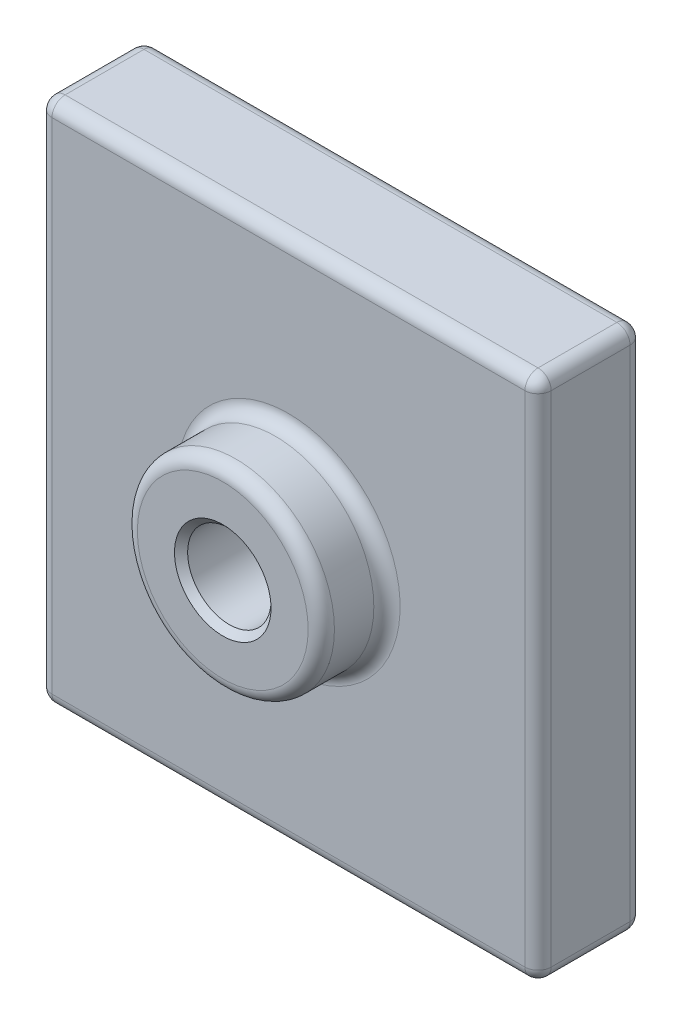
SolidWorks part; units mm, degrees
ref_plane "Front Plane" through (0, 0, 0) normal (0, 0, 1) x (1, 0, 0)
ref_plane "Top Plane" through (0, 0, 0) normal (0, 1, 0) x (1, 0, 0)
ref_plane "Right Plane" through (0, 0, 0) normal (1, 0, 0) x (0, 0, -1)
sketch "Sketch1" plane through (0, 0, 0) normal (0, 0, 1) x (1, 0, 0)
  line L1 (0, 0) -> (38, 0)
  line L2 (0, 0) -> (0, 40)
  line L3 (0, 40) -> (38, 40)
  line L4 (38, 0) -> (38, 40)
  dimension "D1" = 38
  dimension "D2" = 40
extrude "Boss-Extrude1" add sketch "Sketch1" along normal blind 8
sketch "Sketch2" plane through (0, 0, 8) normal (0, 0, 1) x (1, 0, 0)
  line L4 (0, 40) -> (0, 0)
  line L5 (0, 0) -> (38, 0)
  line L6 (38, 0) -> (38, 40)
  line L7 (38, 40) -> (0, 40)
  line L8 (0, 40) -> (0, 0) construction
  line L9 (0, 0) -> (38, 0) construction
  line L10 (38, 0) -> (38, 40) construction
  line L11 (38, 40) -> (0, 40) construction
  circle A0 centre (19, 20) radius 7.5
  circle A1 centre (19, 20) radius 3.175
  point P2 (19, 20)
  point P4 (0, 20)
  point P6 (19, 0)
  dimension "D2" = 15
  dimension "D3" = 6.35
  dimension "D1" = 0
extrude "Boss-Extrude2" add sketch "Sketch2" along normal blind 5
fillet "Fillet1" radius 1 14 edges at (26.5, 20, 13) (19, 0, 0) (19, 40, 0) (38, 0, 4) (38, 40, 4) (38, 20, 0) (0, 40, 4) (0, 0, 4) (0, 20, 0) (26.5, 20, 8) (19, 40, 8) (38, 20, 8) (19, 0, 8) (0, 20, 8)
sketch "Sketch3" plane through (0, 0, 0) normal (0, 0, -1) x (-1, 0, 0)
  line L4 (-1, 39) -> (-37, 39)
  line L5 (-37, 39) -> (-37, 1)
  line L6 (-37, 1) -> (-1, 1)
  line L7 (-1, 1) -> (-1, 39)
  line L8 (-1, 39) -> (-37, 39) construction
  line L9 (-37, 39) -> (-37, 1) construction
  line L10 (-37, 1) -> (-1, 1) construction
  line L11 (-1, 1) -> (-1, 39) construction
  line L15 (-15.7921, 25.5563) -> (-22.2079, 25.5563)
  line L16 (-22.2079, 25.5563) -> (-25.4158, 20)
  line L17 (-25.4158, 20) -> (-22.2079, 14.4438)
  line L18 (-22.2079, 14.4438) -> (-15.7921, 14.4438)
  line L19 (-15.7921, 14.4438) -> (-12.5842, 20)
  line L20 (-12.5842, 20) -> (-15.7921, 25.5563)
  circle A0 centre (-19, 20) radius 5.5562 construction
  point P2 (-19, 39)
  point P4 (-37, 20)
  point P6 (-19, 20)
  dimension "D2" = 11.1125
  dimension "D1" = 0
extrude "Cut-Extrude1" cut sketch "Sketch3" against normal blind 5.5562
sketch "Sketch4" plane through (0, 0, 0) normal (0, 0, -1) x (-1, 0, 0)
  circle A0 centre (-19, 20) radius 3.175 construction
  circle A1 centre (-19, 20) radius 3.175
extrude "Cut-Extrude2" cut sketch "Sketch4" against normal through all
chamfer "Chamfer1" distance 0.5 angle 45 8 edges at (19, 25.5563, 0) (23.8119, 22.7781, 0) (23.8119, 17.2219, 0) (19, 14.4438, 0) (14.1881, 17.2219, 0) (14.1881, 22.7781, 0) (15.825, 20, 5.5562) (22.175, 20, 13)
